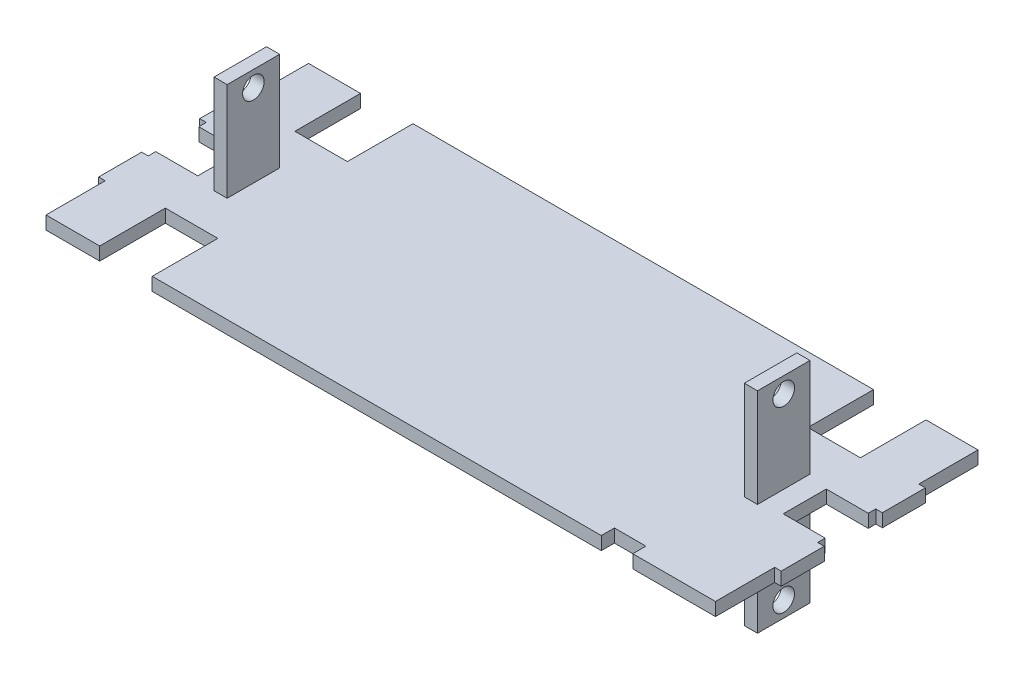
SolidWorks part; units mm, degrees
ref_plane "Front Plane" through (0, 0, 0) normal (0, 0, 1) x (1, 0, 0)
ref_plane "Top Plane" through (0, 0, 0) normal (0, 1, 0) x (1, 0, 0)
ref_plane "Right Plane" through (0, 0, 0) normal (1, 0, 0) x (0, 0, -1)
sketch "Sketch1" plane through (0, 0, 0) normal (0, 1, 0) x (1, 0, 0)
  line L0 (0, 72.39) -> (0, -72.39) construction
  line L1 (161.925, -63.5) -> (121.92, -63.5)
  line L2 (161.925, -63.5) -> (161.925, -34.8747)
  line L3 (161.925, 63.5) -> (136.779, 63.5)
  line L4 (-161.925, -63.5) -> (-161.925, -34.8747)
  line L5 (161.925, -63.5) -> (-161.925, 63.5) construction
  line L6 (161.925, 63.5) -> (-161.925, -63.5) construction
  line L7 (161.925, 10.414) -> (141.605, 10.414)
  line L9 (161.925, -10.414) -> (141.605, -10.414)
  line L10 (141.605, 10.414) -> (141.605, -10.414)
  line L11 (-136.779, 63.5) -> (-161.925, 63.5)
  line L13 (-161.925, -10.414) -> (-141.605, -10.414)
  line L14 (-141.605, 10.414) -> (-141.605, -10.414)
  line L15 (-161.925, 10.414) -> (-141.605, 10.414)
  line L17 (-141.605, 0) -> (127, 0) construction
  line L18 (-161.925, 14.0467) -> (-165.1, 14.0467)
  line L20 (-161.925, 34.8747) -> (-165.1, 34.8747)
  line L21 (-165.1, 14.0467) -> (-165.1, 34.8747)
  line L22 (-161.925, -34.8747) -> (-165.1, -34.8747)
  line L23 (-165.1, -14.0467) -> (-165.1, -34.8747)
  line L24 (-161.925, -14.0467) -> (-165.1, -14.0467)
  line L27 (161.925, -14.0467) -> (165.1, -14.0467)
  line L28 (165.1, -14.0467) -> (165.1, -34.8747)
  line L29 (161.925, -34.8747) -> (165.1, -34.8747)
  line L30 (161.925, 34.8747) -> (165.1, 34.8747)
  line L31 (165.1, 14.0467) -> (165.1, 34.8747)
  line L32 (161.925, 14.0467) -> (165.1, 14.0467)
  line L34 (-161.925, 34.8747) -> (-161.925, 63.5)
  line L35 (-161.925, -14.0467) -> (-161.925, -10.414)
  line L36 (161.925, 34.8747) -> (161.925, 63.5)
  line L37 (161.925, -14.0467) -> (161.925, -10.414)
  line L38 (-161.925, 10.414) -> (-161.925, 14.0467)
  line L39 (161.925, 10.414) -> (161.925, 14.0467)
  line L40 (-136.779, 63.5) -> (-136.779, 31.75)
  line L41 (-136.779, 31.75) -> (-111.379, 31.75)
  line L42 (-111.379, 63.5) -> (-111.379, 31.75)
  line L44 (111.379, 63.5) -> (111.379, 31.75)
  line L45 (111.379, 31.75) -> (136.779, 31.75)
  line L46 (136.779, 63.5) -> (136.779, 31.75)
  line L47 (111.379, 63.5) -> (-111.379, 63.5)
  line L48 (106.68, -63.5) -> (-106.68, -63.5)
  line L50 (106.68, -63.5) -> (106.68, -57.15)
  line L51 (106.68, -57.15) -> (121.92, -57.15)
  line L52 (121.92, -63.5) -> (121.92, -57.15)
  line L56 (-135.9408, -63.5) -> (-161.925, -63.5)
  line L57 (-106.68, -63.5) -> (-110.5408, -63.5)
  line L59 (-135.9408, -63.5) -> (-135.9408, -31.75)
  line L60 (-135.9408, -31.75) -> (-110.5408, -31.75)
  line L61 (-110.5408, -63.5) -> (-110.5408, -31.75)
  point P0 (0, 0)
  point P6 (141.605, 0)
  point P47 (121.92, -60.325)
  point P48 (124.079, 31.75)
  point P49 (-124.079, 31.75)
  point P52 (-123.2408, -31.75)
  dimension "D1" = 323.85
  dimension "D2" = 127
  dimension "D3" = 20.828
  dimension "D5" = 3.175
  dimension "D6" = 20.828
  dimension "D4" = 20.32
  dimension "D7" = 31.75
  dimension "D8" = 25.4
  dimension "D9" = 25.4
  dimension "D10" = 31.75
  dimension "D13" = 15.24
  dimension "D14" = 6.35
  dimension "D15" = 40.005
  dimension "D16" = 25.4
  dimension "D17" = 31.75
  dimension "D18" = 41.8592
  dimension "D11" = 41.021
  dimension "D12" = 41.021
extrude "Boss-Extrude1" add sketch "Sketch1" along normal mid plane 6.35
sketch "Sketch2" plane through (0, 0, 0) normal (0, 1, 0) x (1, 0, 0)
  line L0 (-141.605, 10.414) -> (-141.605, -10.414) construction
  line L1 (125.095, -12.7) -> (131.445, -12.7)
  line L2 (125.095, -12.7) -> (125.095, 12.7)
  line L3 (125.095, 12.7) -> (131.445, 12.7)
  line L4 (131.445, -12.7) -> (131.445, 12.7)
  line L5 (125.095, -12.7) -> (131.445, 12.7) construction
  line L6 (125.095, 12.7) -> (131.445, -12.7) construction
  line L9 (-125.095, -12.7) -> (-125.095, 12.7)
  line L10 (-125.095, 12.7) -> (-131.445, 12.7)
  line L11 (-131.445, -12.7) -> (-131.445, 12.7)
  line L12 (-125.095, -12.7) -> (-131.445, -12.7)
  line L13 (141.605, -10.414) -> (141.605, 10.414) construction
  point P0 (128.27, 0)
  point P10 (141.605, 0)
  dimension "D1" = 10.16
  dimension "D2" = 10.16
  dimension "D3" = 25.4
  dimension "D4" = 25.4
  dimension "D5" = 6.35
  dimension "D6" = 6.35
  dimension "D7" = 6.35
extrude "Boss-Extrude2" add sketch "Sketch2" along normal mid plane 101.6
sketch "Sketch3" plane through (-131.445, 0, 0) normal (-1, 0, 0) x (0, 0, 1)
  line L0 (-12.7, 50.8) -> (12.7, 50.8) construction
  line L1 (-12.7, -50.8) -> (12.7, -50.8) construction
  circle A0 centre (0, 43.18) radius 5.207
  circle A1 centre (0, -43.18) radius 5.207
  point P4 (0, 50.8)
  dimension "D1" = 10.414
  dimension "D2" = 10.414
  dimension "D3" = 7.62
  dimension "D4" = 7.62
  dimension "D5" = 86.36
extrude "Cut-Extrude1" cut sketch "Sketch3" against normal through all both and the other way through all
equation "\"length\"= 12.75"
equation "\"width\"=5"
equation "\"height\"= 0.25"
equation "\"D1@Sketch1\"=\"length\""
equation "\"D2@Sketch1\"=\"width\""
equation "\"eyebolt width\"= 0.82"
equation "\"eyebolt length\"= 0.8"
equation "\"D3@Sketch1\"=\"eyebolt width\""
equation "\"D4@Sketch1\"=\"eyebolt length\""
equation "\"lead screw holder height\"= 2.76"
equation "\"lead screw diameter\"=0.41"
equation "\"D1@Sketch3\"=\"lead screw diameter\""
equation "\"distance from holders to board\"=0.4"
equation "\"D2@Sketch3\"=\"lead screw diameter\""
equation "\"lead_screw_dist\"=3.4"
equation "\"D5@Sketch3\"=\"lead_screw_dist\""
